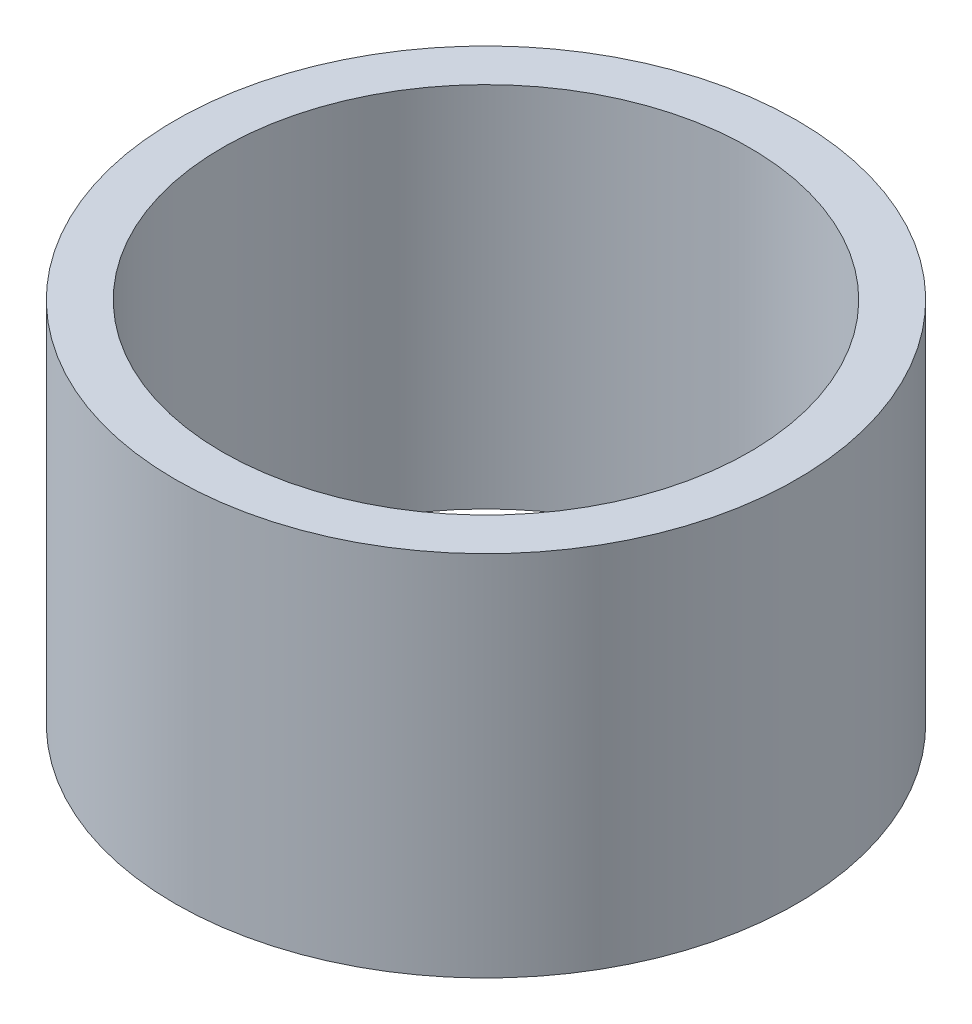
SolidWorks part; units mm, degrees
ref_plane "Front Plane" through (0, 0, 0) normal (0, 0, 1) x (1, 0, 0)
ref_plane "Top Plane" through (0, 0, 0) normal (0, 1, 0) x (1, 0, 0)
ref_plane "Right Plane" through (0, 0, 0) normal (1, 0, 0) x (0, 0, -1)
sketch "Sketch1" plane through (0, 0, 0) normal (0, 1, 0) x (1, 0, 0)
  circle A0 centre (0, 0) radius 27.5
  dimension "SLEEVE_OD" = 55
extrude "Boss-Extrude1" add sketch "Sketch1" along normal blind 32.5046
sketch "Sketch2" plane through (0, 0, 0) normal (0, 1, 0) x (1, 0, 0)
  circle A0 centre (0, 0) radius 23.3138
  dimension "BORE_D" = 46.6277
extrude "Cut-Extrude1" cut sketch "Sketch2" along normal through all
chamfer "Chamfer1" distance 2.7955 angle 30 rebuild error yes
